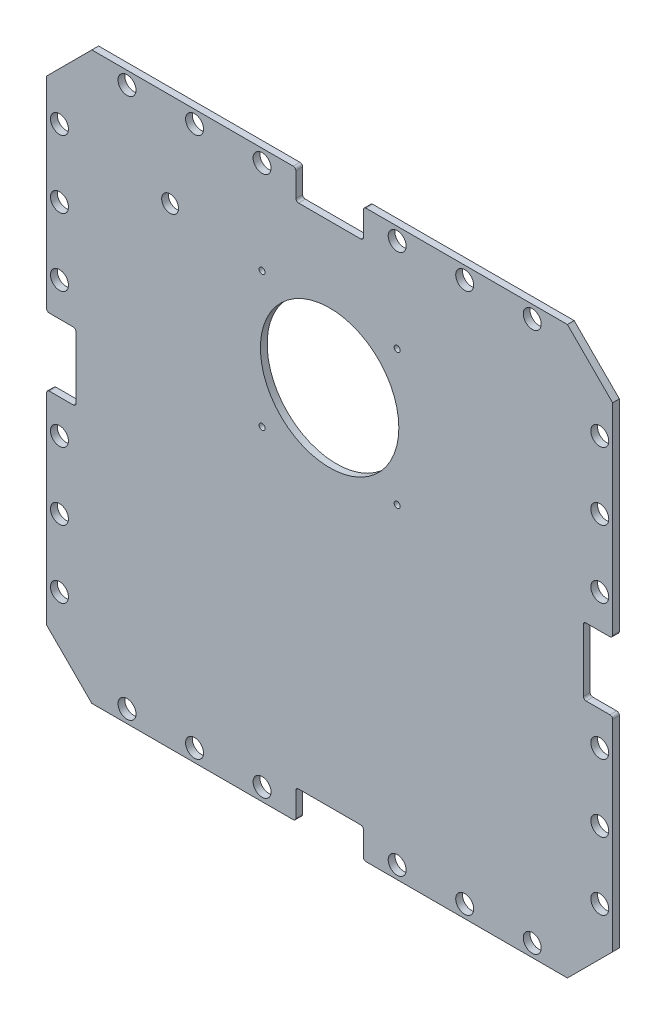
SolidWorks part; units mm, degrees
ref_plane "Front Plane" through (0, 0, 0) normal (0, 0, 1) x (1, 0, 0)
ref_plane "Top Plane" through (0, 0, 0) normal (0, 1, 0) x (1, 0, 0)
ref_plane "Right Plane" through (0, 0, 0) normal (1, 0, 0) x (0, 0, -1)
sketch "Sketch1" plane through (0, 0, 0) normal (0, 0, 1) x (1, 0, 0)
  line L0 (30.226, -4.826) -> (55.626, -4.826) construction
  line L1 (0, 0) -> (212.852, 0)
  line L2 (0, 0) -> (0, -212.852)
  line L3 (0, -212.852) -> (212.852, -212.852)
  line L4 (212.852, 0) -> (212.852, -212.852)
  line L5 (55.626, -4.826) -> (81.026, -4.826) construction
  line L6 (81.026, -4.826) -> (106.426, -4.826) construction
  line L7 (106.426, -4.826) -> (131.826, -4.826) construction
  line L8 (131.826, -4.826) -> (157.226, -4.826) construction
  line L9 (157.226, -4.826) -> (182.626, -4.826) construction
  line L10 (106.426, 0) -> (106.426, -212.852) construction
  line L11 (0, -106.426) -> (212.852, -106.426) construction
  line L12 (16.9978, 0) -> (0, -16.9978)
  line L13 (212.852, -16.9978) -> (195.8542, 0)
  line L14 (195.8542, -212.852) -> (212.852, -195.8542)
  line L15 (0, -195.8542) -> (16.9978, -212.852)
  line L16 (93.726, 0) -> (93.726, -11)
  line L17 (81.026, -39.9429) -> (131.826, -39.9429) construction
  line L18 (81.026, -39.9429) -> (81.026, -90.7429) construction
  line L19 (81.026, -90.7429) -> (131.826, -90.7429) construction
  line L20 (131.826, -39.9429) -> (131.826, -90.7429) construction
  line L21 (106.426, -90.7429) -> (106.426, -39.9429) construction
  line L22 (81.026, -65.3429) -> (131.826, -65.3429) construction
  line L23 (93.726, -11) -> (119.126, -11)
  line L24 (119.126, -11) -> (119.126, 0)
  line L25 (212.852, -93.726) -> (201.852, -93.726)
  line L26 (201.852, -93.726) -> (201.852, -119.126)
  line L27 (201.852, -119.126) -> (212.852, -119.126)
  line L28 (119.126, -212.852) -> (119.126, -201.852)
  line L29 (119.126, -201.852) -> (93.726, -201.852)
  line L30 (93.726, -201.852) -> (93.726, -212.852)
  line L31 (0, -119.126) -> (11, -119.126)
  line L32 (11, -119.126) -> (11, -93.726)
  line L33 (11, -93.726) -> (0, -93.726)
  circle A0 centre (30.226, -4.826) radius 3.38
  circle A1 centre (55.626, -4.826) radius 3.38
  circle A2 centre (81.026, -4.826) radius 3.38
  circle A3 centre (131.826, -4.826) radius 3.38
  circle A4 centre (157.226, -4.826) radius 3.38
  circle A5 centre (182.626, -4.826) radius 3.38
  circle A6 centre (106.426, -4.826) radius 5.1943
  circle A7 centre (208.026, -182.626) radius 3.38
  circle A8 centre (208.026, -157.226) radius 3.38
  circle A9 centre (208.026, -131.826) radius 3.38
  circle A10 centre (208.026, -106.426) radius 5.1943
  circle A11 centre (208.026, -81.026) radius 3.38
  circle A12 centre (208.026, -55.626) radius 3.38
  circle A13 centre (208.026, -30.226) radius 3.38
  circle A14 centre (30.226, -208.026) radius 3.38
  circle A15 centre (55.626, -208.026) radius 3.38
  circle A16 centre (81.026, -208.026) radius 3.38
  circle A17 centre (106.426, -208.026) radius 5.1943
  circle A18 centre (131.826, -208.026) radius 3.38
  circle A19 centre (157.226, -208.026) radius 3.38
  circle A20 centre (182.626, -208.026) radius 3.38
  circle A21 centre (4.826, -30.226) radius 3.38
  circle A22 centre (4.826, -55.626) radius 3.38
  circle A23 centre (4.826, -81.026) radius 3.38
  circle A24 centre (4.826, -106.426) radius 5.1943
  circle A25 centre (4.826, -131.826) radius 3.38
  circle A26 centre (4.826, -157.226) radius 3.38
  circle A27 centre (4.826, -182.626) radius 3.38
  circle A28 centre (106.426, -65.3429) radius 26.035
  circle A29 centre (81.026, -39.9429) radius 1.13
  circle A30 centre (131.826, -39.9429) radius 1.13
  circle A31 centre (131.826, -90.7429) radius 1.13
  circle A32 centre (81.026, -90.7429) radius 1.13
  circle A33 centre (46.426, -35.3429) radius 3.175
  point P14 (106.426, -106.426)
  point P69 (106.426, -106.426)
  point P78 (106.426, -106.426)
  point P88 (106.426, -11)
  point P104 (106.426, -106.426)
  dimension "D1" = 6.76
  dimension "D5" = 10.3886
  dimension "D13" = 52.07
  dimension "D14" = 2.26
  dimension "D19" = 6.35
  dimension "D2" = 30.226
  dimension "D3" = 25.4
  dimension "D4" = 4.826
  dimension "D6" = 212.852
  dimension "D7" = 212.852
  dimension "D9" = 45
  dimension "D10" = 24.0386
  dimension "D12" = 65.3429
  dimension "D15" = 50.8
  dimension "D16" = 25.4
  dimension "D17" = 11
  dimension "D20" = 60
  dimension "D21" = 30
  dimension "D8" = 4
  dimension "D11" = 4
  dimension "D18" = 4
extrude "Boss-Extrude1" add sketch "Sketch1" along normal blind 2.54 contours A24 L2 L3 A17 L4 A10 L1 A6 A27 A26 A25 A23 A22 A21 A20 A19 A18 A16 A15 A14 A13 A12 A11 A9 A8 A7 A5 region at (106.4728, -108.654, 0)
hole_wizard "#4-40 Tapped Hole1" positions "3DSketch1" profile "Sketch2" tap size "#4-40" standard "ANSI Inch" end condition through all
sketch3d "3DSketch1"
  line L0 (81.026, -39.9429, 2.54) -> (81.026, -39.9429, 0) construction
  line L1 (131.826, -39.9429, 2.54) -> (131.826, -39.9429, 0) construction
  line L2 (131.826, -90.7429, 2.54) -> (131.826, -90.7429, 0) construction
  line L3 (81.026, -90.7429, 2.54) -> (81.026, -90.7429, 0) construction
  point P0 (81.026, -39.9429, 2.54)
  point P4 (131.826, -39.9429, 2.54)
  point P8 (131.826, -90.7429, 2.54)
  point P12 (81.026, -90.7429, 2.54)
sketch "Sketch2" plane through (81.026, -39.9429, 2.54) normal (1, 0, 0) x (0, -1, 0)
  line L0 (0, 0) -> (0, 2.54)
  line L1 (0, 2.54) -> (1.1303, 2.54)
  line L2 (1.1303, 2.54) -> (1.1303, 0)
  line L5 (1.1303, 0) -> (0, 0)
  line L11 (0, -6.35) -> (0, 107.95) construction
  dimension "Thru Tap Drill Dia." = 2.2606
  dimension "Thru Tap Drill Depth" = 2.54
cosmetic thread "Hole Thread1" parameters "D2"=2.8448
cosmetic thread "Hole Thread2" parameters "D2"=2.8448
cosmetic thread "Hole Thread3" parameters "D2"=2.8448
cosmetic thread "Hole Thread4" parameters "D2"=2.8448
fillet "Fillet1" radius 1 16 edges at (0, -93.726, 1.27) (11, -93.726, 1.27) (0, -119.126, 1.27) (11, -119.126, 1.27) (93.726, -212.852, 1.27) (93.726, -201.852, 1.27) (119.126, -212.852, 1.27) (119.126, -201.852, 1.27) (212.852, -119.126, 1.27) (201.852, -119.126, 1.27) (212.852, -93.726, 1.27) (201.852, -93.726, 1.27) (119.126, -11, 1.27) (119.126, 0, 1.27) (93.726, -11, 1.27) (93.726, 0, 1.27)
